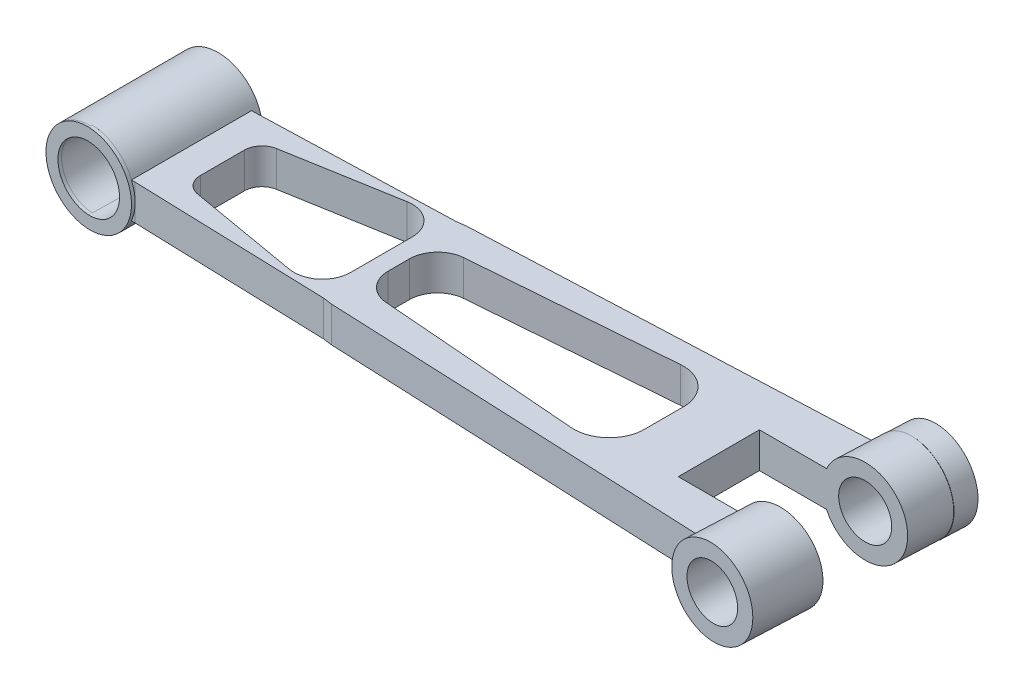
SolidWorks part; units mm, degrees
ref_plane "Front Plane" through (0, 0, 0) normal (0, 0, 1) x (1, 0, 0)
ref_plane "Top Plane" through (0, 0, 0) normal (0, 1, 0) x (1, 0, 0)
ref_plane "Right Plane" through (0, 0, 0) normal (1, 0, 0) x (0, 0, -1)
sketch "Sketch16" plane through (0, 0, 0) normal (0, 1, 0) x (1, 0, 0)
  line L0 (-39.4685, 0) -> (160.7786, 0) construction
  line L6 (0, 17) -> (0, 0)
  line L7 (0, 0) -> (0, -17)
  line L9 (0, 17) -> (25, 17)
  line L11 (0, -17) -> (25, -17)
  line L12 (25, 17) -> (25, -17)
  line L13 (25, 17) -> (80.1092, 18.7564)
  line L14 (25, -17) -> (80.1092, -18.7564)
  line L15 (32.6092, 6.2967) -> (32.6092, -6.1567)
  line L16 (36.756, -11.0833) -> (68.244, -16.5367)
  line L17 (77.6092, -8.654) -> (77.6092, 8.794)
  line L18 (68.244, 16.6767) -> (36.756, 11.2233)
  line L23 (80.1092, -18.7564) -> (80.1092, 18.7564)
  arc A0 (32.6092, 6.2967) -> (36.756, 11.2233) centre (37.6092, 6.2967) cw
  arc A1 (36.756, -11.0833) -> (32.6092, -6.1567) centre (37.6092, -6.1567) cw
  arc A2 (77.6092, 8.794) -> (68.244, 16.6767) centre (69.6092, 8.794) ccw
  arc A3 (77.6092, -8.654) -> (68.244, -16.5367) centre (69.6092, -8.654) cw
  point P22 (52.5, 13.95)
  point P26 (12.5, 17)
  dimension "D7" = 8
  dimension "D8" = 8
  dimension "D9" = 45
  dimension "D10" = 40
  dimension "D5" = 5
  dimension "D6" = 5
  dimension "D1" = 17
  dimension "D2" = 25
  dimension "D3" = 1.826
  dimension "D4" = 1.826
  dimension "D11" = 8
  dimension "D12" = 8
  dimension "18" = 17
extrude "Boss-Extrude6" add sketch "Sketch16" along normal blind 10 contours L6 L0 L12 L9 | L0 L7 L11 L12 | L0 L12 L14 L23 L17 A3 L16 A1 L15 | L12 L0 L15 A0 L18 A2 L17 L23 L13 region at (12.5, 0, -8.5) region at (12.5, 0, 8.5) region at (25.5821, 0, -8.5) region at (28.8046, 0, 0.5821)
sketch "Sketch17" plane through (0, 10, 0) normal (0, 1, 0) x (1, 0, 0)
  line L0 (80.1092, 18.7564) -> (80.1092, -18.7564)
  line L1 (80.1092, -18.7564) -> (82.5867, -19.091)
  line L2 (80.1092, 18.7564) -> (82.5867, 19.091)
  line L3 (82.5867, 19.091) -> (162.5867, 22.5838)
  line L4 (82.5867, -19.091) -> (162.5867, -22.5838)
  line L5 (-28.5581, 0) -> (196.6242, 0) construction
  line L7 (89.9591, -10.9753) -> (146.8137, -15.4499)
  line L9 (146.8137, 15.4499) -> (89.9591, 10.9753)
  line L10 (157.5867, -5) -> (157.5867, 0)
  line L11 (157.5867, 0) -> (157.5867, 5)
  line L12 (82.5867, 3) -> (82.5867, 0)
  line L13 (82.5867, 0) -> (82.5867, -3)
  line L14 (157.5867, -35.1361) -> (162.5867, -35.1361)
  line L15 (162.5867, -22.5838) -> (162.5867, 22.5838)
  arc A0 (89.9591, 10.9753) -> (82.5867, 3) centre (90.5867, 3) ccw
  arc A1 (89.9591, -10.9753) -> (82.5867, -3) centre (90.5867, -3) cw
  arc A2 (157.5867, 5) -> (146.8137, 15.4499) centre (147.5983, 5.4807) ccw
  arc A3 (157.5867, -5) -> (146.8137, -15.4499) centre (147.5983, -5.4807) cw
  line M24 (80.1092, -18.7564) -> (80.1092, 18.7564)
  dimension "D7" = 8
  dimension "D8" = 8
  dimension "D9" = 10
  dimension "D10" = 10
  dimension "D1" = 2.5
  dimension "D2" = 2.5
  dimension "D3" = 2.5
  dimension "D4" = 2.5
  dimension "D5" = 80
  dimension "D6" = 80
  dimension "D11" = 3
  dimension "D12" = 2
  dimension "D13" = 3
  dimension "D14" = 5
  dimension "D15" = 5
  dimension "D16" = 75
  dimension "D17" = 2
  dimension "D18" = 5
extrude "Boss-Extrude7" add sketch "Sketch17" against normal blind 10 contours L0 L5 L12 A0 L9 A2 L11 L15 L3 L2 | L5 L1 L4 L15 L10 A3 L7 A1 L13 M24 region at (122.6674, 10, -15.3555) region at (122.6674, 10, 15.3555)
sketch "Sketch18" plane through (0, 10, 0) normal (0, 1, 0) x (1, 0, 0)
  line L0 (162.5867, 22.5838) -> (204.5867, 24.4176)
  line L1 (162.5867, -22.5838) -> (204.5867, -24.4176)
  line L2 (-18.3572, 0) -> (268.6924, 0) construction
  line L3 (204.5867, 24.4176) -> (204.5867, -24.4176)
  line L4 (162.5867, 22.5838) -> (162.5867, -22.5838)
  dimension "D1" = 2.5
  dimension "D2" = 2.5
  dimension "D3" = 42
  dimension "D4" = 42
extrude "Boss-Extrude9" add sketch "Sketch18" against normal blind 10 contours L0 L3 L1 L4
sketch "Sketch19" plane through (0, 0, 17) normal (0, 0, 1) x (1, 0, 0)
  line L0 (-19.1577, 5) -> (35.868, 5) construction
  circle A0 centre (12.5, 5) radius 12.5
  dimension "D1" = 25
extrude "Boss-Extrude10" add sketch "Sketch19" against normal blind 35
sketch "Sketch20" plane through (0, 0, 17) normal (0, 0, 1) x (1, 0, 0)
  line L0 (0, 10) -> (1.0436, 10)
  line L1 (1.0436, 10) -> (1.0436, 0)
  line L2 (1.0436, 0) -> (0, 0)
  line L3 (0, 0) -> (0, 10)
extrude "Cut-Extrude3" cut sketch "Sketch20" against normal through all
sketch "Sketch21" plane through (0, 0, 17) normal (0, 0, 1) x (1, 0, 0)
  circle A0 centre (12.5, 5) radius 12.5
  dimension "D1" = 25
extrude "Boss-Extrude11" add sketch "Sketch21" against normal blind 36
sketch "Sketch22" plane through (0, 0, 17) normal (0, 0, 1) x (1, 0, 0)
  circle A0 centre (12.5, 5) radius 9
  dimension "D1" = 18
extrude "Cut-Extrude4" cut sketch "Sketch22" against normal through all
sketch "Sketch23" plane through (-0.6748, 0, 15.4557) normal (-0.0436, 0, 0.999) x (0.999, 0, 0.0436)
  circle A0 centre (203.2296, 5) radius 12
  dimension "D2" = 24
extrude "Boss-Extrude12" add sketch "Sketch23" against normal blind 48 contours A0
sketch "Sketch24" plane through (-0.5159, 0, 16.1868) normal (-0.0319, 0, 0.9995) x (0.9995, 0, 0.0319)
  circle A0 centre (13.0352, 5) radius 12.5
  dimension "D1" = 25
extrude "Boss-Extrude13" add sketch "Sketch24" along normal blind 1
sketch "Sketch25" plane through (-0.5478, 0, 17.1863) normal (-0.0319, 0, 0.9995) x (0.9995, 0, 0.0319)
  circle A0 centre (13.0352, 5) radius 9
  dimension "D1" = 18
extrude "Cut-Extrude5" cut sketch "Sketch25" against normal through all
sketch "Sketch26" plane through (-0.6748, 0, 15.4557) normal (-0.0436, 0, 0.999) x (0.999, 0, 0.0436)
  circle A0 centre (203.2296, 5) radius 12
extrude "Boss-Extrude14" add sketch "Sketch26" along normal blind 6.5
sketch "Sketch27" plane through (1.4189, 0, -32.4986) normal (0.0436, 0, -0.999) x (-0.999, 0, -0.0436)
  line L0 (-203.3269, 0) -> (-203.3269, 10) construction
  circle A0 centre (-203.3269, 5) radius 12
  dimension "D1" = 24
extrude "Boss-Extrude15" add sketch "Sketch27" along normal blind 6.5 contours A0
sketch "Sketch29" plane through (-0.9583, 0, 21.9495) normal (-0.0436, 0, 0.999) x (0.999, 0, 0.0436)
  circle A0 centre (203.2296, 5) radius 7.5
  dimension "D1" = 15
extrude "Cut-Extrude6" cut sketch "Sketch29" against normal through all
sketch "Sketch30" plane through (0, 10, 0) normal (0, 1, 0) x (1, 0, 0)
  line L0 (215.9654, 10.6194) -> (173.9654, 10.6194)
  line L3 (173.9654, 10.6194) -> (173.9654, -12.3377)
  line L4 (173.9654, -12.3377) -> (215.1708, -12.3377)
  line L5 (215.9654, 10.6194) -> (215.1708, -12.3377)
  dimension "D4" = 42
extrude "Cut-Extrude8" cut sketch "Sketch30" against normal mid plane 70 contours L0 L3 L4 L5
